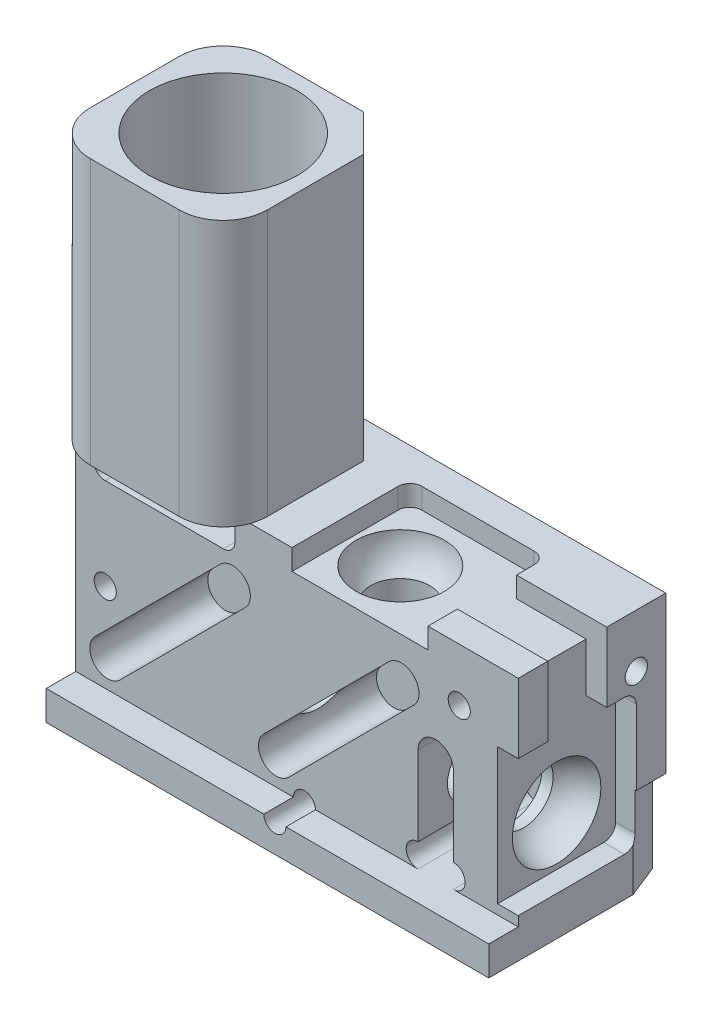
SolidWorks part; units mm, degrees
ref_plane "Front Plane" through (0, 0, 0) normal (0, 0, 1) x (1, 0, 0)
ref_plane "Top Plane" through (0, 0, 0) normal (0, 1, 0) x (1, 0, 0)
ref_plane "Right Plane" through (0, 0, 0) normal (1, 0, 0) x (0, 0, -1)
sketch "Sketch1" plane through (0, 0, 0) normal (0, 1, 0) x (1, 0, 0)
  line L1 (7.5, 3) -> (-7.5, 3)
  line L2 (7.5, 3) -> (7.5, -3)
  line L3 (7.5, -3) -> (-7.5, -3)
  line L4 (-7.5, 3) -> (-7.5, -3)
  line L5 (7.5, 3) -> (-7.5, -3) construction
  line L6 (7.5, -3) -> (-7.5, 3) construction
  point P0 (0, 0)
  dimension "D1" = 6
  dimension "D2" = 15
extrude "Main Body Ext" add sketch "Sketch1" along normal blind 8.3
sketch "Sketch8" plane through (0, 8.3, 0) normal (0, 1, 0) x (1, 0, 0)
  line L0 (-2.75, 3) -> (-1.5, 1.75)
  line L1 (-2.75, 3) -> (-7.5, 3)
  line L2 (-1.5, 1.75) -> (-1.5, -3)
  line L3 (-1.5, -3) -> (-7.5, -3)
  line L4 (-7.5, 3) -> (-7.5, -3)
  line L5 (-2.125, 2.375) -> (-7.5, -3) construction
  line L6 (-1.5, -3) -> (-7.5, 3) construction
  line L7 (-7.5, 3) -> (-7.5, -3) construction
  line L8 (0, 0) -> (-4.5, 0) construction
  point P0 (-4.5, 0)
  dimension "D1" = 6
  dimension "D2" = 6
  dimension "D3" = 1.25
  dimension "D4" = 3
extrude "Emission Path Ext" add sketch "Sketch8" along normal blind 9
sketch "Sketch3" plane through (0, 0, 0) normal (0, -1, 0) x (1, 0, 0)
  line L0 (-7.5, -3) -> (-7.5, 3) construction
  line L1 (0, 0) -> (-4.5, 0) construction
  circle A0 centre (-4.5, 0) radius 1.25
  dimension "D1" = 3
  dimension "D2" = 2.5
extrude "Emission and Grin Cut" cut sketch "Sketch3" against normal through all
sketch "Sketch4" plane through (7.5, 0, 0) normal (1, 0, 0) x (0, 0, -1)
  line L1 (-3, 0) -> (3, 0) construction
  circle A0 centre (0, 3) radius 1
  dimension "D1" = 2
  dimension "D2" = 3
extrude "Drum Lens Cut" cut sketch "Sketch4" against normal offset from surface (13 mm away) 2 up to face at (-7.5, 8.65, 0)
sketch "Sketch41" plane through (0, 8.3, 0) normal (0, 1, 0) x (1, 0, 0)
  line L1 (7.5, 3) -> (-2.75, 3) construction
  line L2 (-1.5, -3) -> (-1.5, 1.75) construction
  circle A0 centre (1.5, 0) radius 1
  dimension "D1" = 2
  dimension "D2" = 3
  dimension "D3" = 3
extrude "Addtl Light Source" cut sketch "Sketch41" against normal blind 5
sketch "Sketch5" plane through (0, 0, 3) normal (0, 0, 1) x (1, 0, 0)
  line L0 (-7.5, 0) -> (7.5, 0) construction
  line L1 (7.5, 8.3) -> (-7.5, 8.3)
  line L2 (7.5, 8.3) -> (7.5, 1)
  line L3 (7.5, 1) -> (-7.5, 1)
  line L4 (-7.5, 8.3) -> (-7.5, 1)
  line L5 (7.5, 8.3) -> (-7.5, 1) construction
  line L6 (7.5, 1) -> (-7.5, 8.3) construction
  line L7 (-1.5, 8.3) -> (7.5, 8.3) construction
  line L9 (7.5, 8.3) -> (7.5, 0) construction
  line L10 (-7.5, 17.3) -> (-7.5, 0) construction
  point P0 (0, 4.65)
  dimension "D1" = 1
extrude "FilterSet Cut1" cut sketch "Sketch5" against normal blind 1
sketch "Sketch6" plane through (0, 0, 2) normal (0, 0, 1) x (1, 0, 0)
  line L0 (5.3, 4.5) -> (5.3, 1.8)
  line L1 (4.1, 4.5) -> (5.3, 4.5) construction
  line L2 (5.3, 1) -> (4.1, 1)
  line L3 (-7.5, 1) -> (7.5, 1) construction
  line L4 (-7.5, 8.3) -> (-7.5, 1) construction
  line L5 (-6.9, 7.9) -> (-6.9, 7.5)
  line L6 (4.1, 4.5) -> (4.1, 1.8)
  line L7 (-1.5, 8.3) -> (-7.5, 8.3) construction
  line L8 (-2.1, 7.9) -> (-2.1, 7.5)
  line L9 (-6, 1.5) -> (-6, 1) construction
  line L10 (-2.5, 8.3) -> (-6.5, 8.3)
  line L11 (-4.5, 3) -> (-4.5, 1) construction
  line L12 (-4.5, 3) -> (0.4851, 3) construction
  line L13 (-2.5, 7.1) -> (-6.5, 7.1)
  line L14 (-0.282, 1.5) -> (-0.282, 1) construction
  line L15 (-2.5, 8.3) -> (-6.5, 7.1) construction
  line L16 (-2.5, 7.1) -> (-6.5, 8.3) construction
  line L17 (4.1, 1.8) -> (5.3, 1.8) construction
  line L18 (-2.6059, 6.5912) -> (-6.8485, 2.3485)
  line L19 (7.5, 1) -> (7.5, 8.3) construction
  line L20 (-1.7574, 5.7426) -> (-6, 1.5)
  line L21 (-2.6059, 6.5912) -> (-6, 1.5) construction
  line L22 (-6.8485, 2.3485) -> (-1.7574, 5.7426) construction
  line L23 (1.826, 3.6081) -> (1.826, 1.6081) construction
  line L24 (1.826, 3.6081) -> (3.2165, 3.6081) construction
  line L25 (3.1121, 6.5912) -> (-1.1305, 2.3485)
  line L26 (3.9606, 5.7426) -> (-0.282, 1.5)
  line L27 (3.1121, 6.5912) -> (-0.282, 1.5) construction
  line L28 (-1.1305, 2.3485) -> (3.9606, 5.7426) construction
  line L33 (-2.5, 8.3) -> (1.102, 8.3) construction
  line L34 (1.102, 8.3) -> (1.102, 7.1) construction
  line L35 (1.102, 7.1) -> (-2.5, 7.1) construction
  line L36 (-6.5, 7.1) -> (-4.098, 7.1) construction
  line L37 (-4.098, 7.1) -> (-4.098, 8.3) construction
  line L38 (-4.098, 8.3) -> (-6.5, 8.3) construction
  line L39 (-6.5, 8.3) -> (-2.7284, 6.992) construction
  arc A0 (-2.5, 8.3) -> (-2.1, 7.9) centre (-2.5, 7.9) cw
  arc A1 (4.1, 4.5) -> (5.3, 4.5) centre (4.7, 4.5) cw
  arc A2 (-6.5, 8.3) -> (-6.9, 7.9) centre (-6.5, 7.9) ccw
  arc A3 (-2.6059, 6.5912) -> (-1.7574, 5.7426) centre (-2.1816, 6.1669) cw
  arc A4 (4.1, 1) -> (4.1, 1.8) centre (4.1, 1.4) cw
  arc A5 (-6.8485, 2.3485) -> (-6, 1.5) centre (-6.4243, 1.9243) ccw
  arc A6 (5.3, 1) -> (5.3, 1.8) centre (5.3, 1.4) ccw
  arc A7 (-6.5, 7.1) -> (-6.9, 7.5) centre (-6.5, 7.5) cw
  arc A8 (-2.5, 7.1) -> (-2.1, 7.5) centre (-2.5, 7.5) ccw
  arc A9 (3.1121, 6.5912) -> (3.9606, 5.7426) centre (3.5364, 6.1669) cw
  arc A10 (-1.1305, 2.3485) -> (-0.282, 1.5) centre (-0.7063, 1.9243) ccw
  point P5 (-4.5, 7.7)
  point P10 (-4.3029, 4.0456)
  point P21 (1.415, 4.0456)
  dimension "D10" = 0.5
  dimension "D5" = 2.2
  dimension "D8" = 0.4
  dimension "D11" = 0.4
  dimension "D12" = 0.4
  dimension "D1" = 1.2
  dimension "D2" = 45
  dimension "D3" = 3.5
  dimension "D4" = 1.2
  dimension "D6" = 2
  dimension "D7" = 4
  dimension "D9" = 3
  dimension "D13" = 1.2
  dimension "D14" = 3
  dimension "D15" = 6
  dimension "D16" = 45
  dimension "D17" = 0.5
  dimension "D18" = 1.2
  dimension "D19" = 2
  dimension "D20" = 6
extrude "FilterSet Cut2" cut sketch "Sketch6" against normal offset from surface (4 mm away) 1 up to face at (-0.0625, 9.2833, -3)
sketch "Sketch10" plane through (0, 17.3, 0) normal (0, 1, 0) x (1, 0, 0)
  line L0 (-4.5, 0) -> (-4.5, -3) construction
  line L1 (-7.5, -3) -> (-1.5, -3) construction
  line L3 (-4.5, 0) -> (-7.5, 0) construction
  line L4 (-7.5, 3) -> (-7.5, -3) construction
  circle A0 centre (-4.5, 0) radius 2.5
  dimension "D1" = 5
extrude "Emission Lens Cut" cut sketch "Sketch10" against normal offset from surface (8.5 mm away) 0.5 up to face at (-4.125, 8.3, 1.3125)
sketch "Sketch12" plane through (7.5, 0, 0) normal (1, 0, 0) x (0, 0, -1)
  line L0 (0, 3.635) -> (0, 0) construction
  line L1 (1.6, 5.94) -> (-1.6, 5.94)
  line L2 (1.6, 5.94) -> (1.6, 1.33) construction
  line L3 (-2, 1.33) -> (1.6, 1.33)
  line L4 (-1.6, 5.94) -> (-1.6, 1.33) construction
  line L5 (1.6, 5.94) -> (-1.6, 1.33) construction
  line L6 (1.6, 1.33) -> (-1.6, 5.94) construction
  line L7 (-3, 0) -> (3, 0) construction
  line L9 (-1.6, 5.94) -> (-2, 5.94)
  line L10 (-2, 1) -> (-2, 8.3) construction
  line L11 (-2, 5.94) -> (-2, 1.33)
  line L12 (2, 5.54) -> (2, 1.73)
  arc A1 (1.6, 5.94) -> (2, 5.54) centre (1.6, 5.54) cw
  arc A2 (1.6, 1.33) -> (2, 1.73) centre (1.6, 1.73) ccw
  circle A3 centre (0, 3) radius 1 construction
  point P0 (0, 3.635)
  dimension "D2" = 4.61
  dimension "D3" = 1.67
  dimension "D1" = 3.2
  dimension "D4" = 0.4
sketch "Sketch15" plane through (0, 0, 0) normal (0, -1, 0) x (1, 0, 0)
  line L0 (-6.25, 1.875) -> (-6.25, -1.875) construction
  line L2 (2.5, 0) -> (-4.5, 0) construction
  line L3 (-4.5, 0) -> (-6.25, 0) construction
  circle A0 centre (-6.25, -1.875) radius 0.795
  circle A1 centre (-6.25, 1.875) radius 0.795
  circle A2 centre (2.5, 0) radius 0.795
  dimension "D4" = 1.59
  dimension "D1" = 3.75
  dimension "D2" = 7
  dimension "D3" = 1.75
extrude "Magnets Cut" cut sketch "Sketch15" against normal blind 0.9
sketch "Sketch18" plane through (0, 0, 2) normal (0, 0, 1) x (1, 0, 0)
  line L0 (-7.5, 8.3) -> (-7.5, 1) construction
  line L1 (7.5, 1) -> (7.5, 8.3) construction
  line L2 (7.5, 8.3) -> (-1.5, 8.3) construction
  line L3 (-7.5, 0) -> (7.5, 0) construction
  line L7 (-7.5, 1) -> (4.1, 1) construction
  line L9 (-7.5, 1) -> (-7.5, 0) construction
  circle A0 centre (-6.5, 4) radius 0.375
  circle A1 centre (5.5, 6.5) radius 0.375
  circle A2 centre (0.25, 1) radius 0.375
  dimension "D1" = 0.75
  dimension "D2" = 1
  dimension "D3" = 1.8
  dimension "D4" = 2
  dimension "D5" = 3
  dimension "D6" = 1
  dimension "D7" = 7.75
extrude "Screw Holes Cut" cut sketch "Sketch18" against normal blind 3 and the other way through all
fillet "External Fillet 1" radius 1.5 2 edges at (-7.5, 8.65, -3)
sketch "Sketch14" plane through (0, 0, 0) normal (0, -1, 0) x (1, 0, 0)
  line L0 (7.5, -3) -> (7.5, -1.8916)
  line L1 (7.5, 3) -> (7.5, -3) construction
  line L2 (7.5, -1.8916) -> (7.0566, -3)
  line L3 (7.5, -3) -> (-6, -3) construction
  line L4 (7.0566, -3) -> (7.5, -3)
  line L5 (7.5, -3) -> (-7.5, 3) construction
  line L6 (-7.5, -1.5) -> (-7.5, 3) construction
  line L7 (-7.5, 3) -> (7.5, 3) construction
  dimension "D1" = 1.1938
sketch "Sketch28" plane through (0, 7.1, 0) normal (0, 1, 0) x (1, 0, 0)
  circle A0 centre (-4.5, 0) radius 1.5
  dimension "D1" = 3
extrude "Cut-Extrude8" cut sketch "Sketch28" against normal blind 4 and the other way through all
extrude "Cut-Extrude9" cut sketch "Sketch14" against normal blind 3
extrude "Cut-Extrude Original Light" cut sketch "Sketch12" against normal blind 0.7
sketch "Sketch44" plane through (0, 8.3, 0) normal (0, 1, 0) x (1, 0, 0)
  line L0 (-0.17, -2) -> (4.44, -2)
  line L1 (-0.17, -2) -> (-0.17, 1.6)
  line L2 (4.44, -2) -> (4.44, 1.6)
  line L3 (0.23, 2) -> (4.04, 2)
  line L6 (7.5, -2) -> (-1.5858, -2) construction
  circle A0 centre (1.5, 0) radius 1 construction
  arc A1 (4.44, 1.6) -> (4.04, 2) centre (4.04, 1.6) ccw
  arc A2 (-0.17, 1.6) -> (0.23, 2) centre (0.23, 1.6) cw
  point P10 (4.44, 2)
  point P13 (-0.17, 2)
  dimension "D3" = 1.67
  dimension "D4" = 0.4
  dimension "D5" = 0.4
  dimension "D1" = 4
  dimension "D2" = 4.61
extrude "Cut-Extrude Addtl Light" cut sketch "Sketch44" against normal blind 0.7
sketch "Sketch29" plane through (7.5, 0, 0) normal (1, 0, 0) x (0, 0, -1)
  line L0 (3, 8.3) -> (3, 3) construction
  line L1 (-2, 8.3) -> (3, 8.3) construction
  circle A0 centre (2, 6.5) radius 0.375
  dimension "D1" = 0.75
  dimension "D2" = 1
  dimension "D3" = 1.8
extrude "Cut-Extrude11" cut sketch "Sketch29" against normal blind 2.5
sketch "Sketch31" plane through (6.8, 0, 0) normal (1, 0, 0) x (0, 0, -1)
  circle A0 centre (0, 3) radius 1.6
  dimension "D1" = 3.2
sketch "Sketch32" plane through (7.5, 0, 0) normal (1, 0, 0) x (0, 0, -1)
  line L0 (-2, 8.3) -> (3, 8.3) construction
  line L1 (-1, 8.3) -> (1, 8.3)
  line L2 (-1, 8.3) -> (-1, 5.94)
  line L3 (-1, 5.94) -> (1, 5.94)
  line L4 (1, 8.3) -> (1, 5.94)
  line L5 (1.6, 5.94) -> (-2, 5.94) construction
  line L6 (-2, 5.94) -> (-2, 8.3) construction
  line L8 (3, 8.3) -> (3, 3) construction
  dimension "D1" = 1
  dimension "D2" = 2
extrude "Cut-Extrude14" cut sketch "Sketch32" against normal up to surface (0.7 mm away) up to face at (6.8, 3.635, -0.5609)
sketch "Sketch45" plane through (0, 8.3, 0) normal (0, 1, 0) x (1, 0, 0)
  line L1 (4.44, -1) -> (6.8, -1)
  line L2 (4.44, -1) -> (4.44, 1)
  line L3 (4.44, 1) -> (6.8, 1)
  line L4 (6.8, -1) -> (6.8, 1)
  line L5 (4.44, -1) -> (6.8, 1) construction
  line L6 (4.44, 1) -> (6.8, -1) construction
  line L7 (6.8, 1) -> (6.8, -1) construction
  line L8 (4.44, -2) -> (4.44, 1.6) construction
  line L12 (6.8, -1) -> (7.5, -1) construction
  line L13 (6.8, 1) -> (7.5, 1) construction
extrude "Cut-Extrude19" cut sketch "Sketch45" against normal blind 0.7
sketch "Sketch33" plane through (0, 0, 0) normal (0, 0, 1) x (1, 0, 0)
  line L0 (6.8, 3) -> (5.3, 3)
  line L1 (6.8, 1.4) -> (6.8, 4.6) construction
  line L2 (6.8, 3) -> (6.8, 4.5)
  arc A0 (5.3, 3) -> (6.8, 4.5) centre (6.8, 3) cw
  dimension "D2" = 1.5
revolve "Cut-Revolve1" cut sketch "Sketch33" angle 360 about L0
sketch "Sketch46" plane through (0, 7.6, 0) normal (0, 1, 0) x (1, 0, 0)
  circle A0 centre (1.5, 0) radius 1.5 construction
ref_plane "Plane1" through (1.5, 0, 0) normal (1, 0, 0) x (0, 0, -1)
sketch "Sketch47" plane through (1.5, 0, 0) normal (1, 0, 0) x (0, 0, -1)
  line L4 (-1.5, 7.6) -> (0, 7.6)
  line L5 (0, 7.6) -> (0, 6.1373)
  line L6 (1, 7.6) -> (-1, 7.6) construction
  arc A0 (0, 6.1373) -> (-1.5, 7.6) centre (0, 7.6378) cw
revolve "Cut-Revolve2" cut sketch "Sketch47" angle 360 about L5
sketch "Sketch36" plane through (0, 17.3, 0) normal (0, 1, 0) x (1, 0, 0)
  line L0 (-7.5, -1.5) -> (-7.5, -3)
  line L1 (-7.5, 1.5) -> (-7.5, -3) construction
  line L2 (-7.5, -3) -> (-6, -3)
  line L3 (-7.5, -3) -> (-3, -3) construction
  arc A0 (-7.5, -1.5) -> (-6, -3) centre (-6, -1.5) ccw
  dimension "D1" = 1.5
  dimension "D2" = 1.5
extrude "Cut-Extrude16" cut sketch "Sketch36" against normal up to surface (9 mm away) up to face at (-6, 8.3, 0)
sketch "Sketch37" plane through (0, 8.8, 0) normal (0, 1, 0) x (1, 0, 0)
  circle A0 centre (-4.5, 0) radius 2
  circle A1 centre (-4.5, 0) radius 1.5 construction
  dimension "D1" = 4
extrude "Cut-Extrude17" cut sketch "Sketch37" against normal up to next
